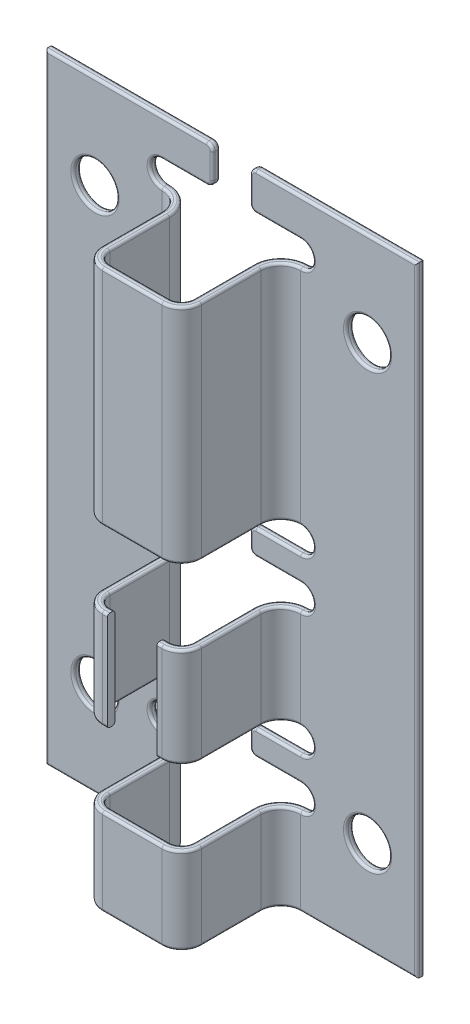
SolidWorks part; units mm, degrees
ref_plane "前视基准面" through (0, 0, 0) normal (0, 0, 1) x (1, 0, 0)
ref_plane "上视基准面" through (0, 0, 0) normal (0, 1, 0) x (1, 0, 0)
ref_plane "右视基准面" through (0, 0, 0) normal (1, 0, 0) x (0, 0, -1)
sketch "草图1" plane through (0, 0, 0) normal (0, 0, 1) x (1, 0, 0)
  line L0 (0, 0) -> (0, 23.061) construction
  line L1 (-15, 25) -> (15, 25)
  line L2 (-15, 25) -> (-15, -25)
  line L3 (-15, -25) -> (15, -25)
  line L4 (15, 25) -> (15, -25)
  line L5 (0, 0) -> (13.1803, 0) construction
  circle A0 centre (11, 17.5) radius 1.75
  circle A1 centre (-11, 17.5) radius 1.75
  circle A2 centre (11, -17.5) radius 1.75
  circle A3 centre (-11, -17.5) radius 1.75
  dimension "D3" = 3.5
  dimension "D4" = 22
  dimension "D5" = 35
  dimension "D1" = 30
  dimension "D2" = 50
extrude "凸台-拉伸1" add sketch "草图1" along normal blind 0.6
sketch "草图3" plane through (0, 25, 0) normal (0, 1, 0) x (1, 0, 0)
  line L0 (-4, -0.6) -> (-4, -8.6)
  line L1 (15, -0.6) -> (-15, -0.6) construction
  line L2 (-4, -8.6) -> (4, -8.6)
  line L3 (4, -8.6) -> (4, -0.6)
  line L4 (0, 0) -> (0, -3.0112) construction
  line L5 (-3.4, -0.6) -> (-3.4, -8)
  line L6 (-3.4, -8) -> (3.4, -8)
  line L7 (3.4, -8) -> (3.4, -0.6)
  line L8 (-4, -0.6) -> (-3.4, -0.6)
  line L9 (4, -0.6) -> (3.4, -0.6)
  dimension "D1" = 8
  dimension "D2" = 8
  dimension "D3" = 0.6
extrude "凸台-拉伸2" add sketch "草图3" against normal up to surface (50 mm away) up to face at (0, -25, 0.3)
sketch "草图4" plane through (0, 0, 8.6) normal (0, 0, 1) x (1, 0, 0)
  line L0 (4, -25) -> (4, 25) construction
  line L1 (-4, 25) -> (4, 25)
  line L2 (-4, 25) -> (-4, 20)
  line L3 (-4, 20) -> (4, 20)
  line L4 (4, 25) -> (4, 20)
  line L5 (-4, -25) -> (-4, 25) construction
  line L6 (-4, 2) -> (4, 2)
  line L7 (-4, 2) -> (-4, -4)
  line L8 (-4, -4) -> (4, -4)
  line L9 (4, 2) -> (4, -4)
  line L10 (4, -25) -> (4, 25) construction
  line L11 (-4, -25) -> (-4, 25) construction
  line L12 (-4, -12) -> (4, -12)
  line L13 (-4, -12) -> (-4, -18)
  line L14 (-4, -18) -> (4, -18)
  line L15 (4, -12) -> (4, -18)
  dimension "D1" = 5
  dimension "D2" = 18
  dimension "D3" = 6
  dimension "D4" = 8
  dimension "D5" = 6
extrude "切除-拉伸1" cut sketch "草图4" against normal up to surface (8 mm away) up to face at (9.5, 0, 0.6)
fillet "圆角1" radius 1 6 edges at (3.4, -21.5, 8) (-3.4, -21.5, 8) (-3.4, -8, 8) (3.4, -8, 8) (3.4, 11, 8) (-3.4, 11, 8)
fillet "圆角2" radius 1.6 6 edges at (-4, -21.5, 8.6) (4, -21.5, 8.6) (-4, -8, 8.6) (4, -8, 8.6) (4, 11, 8.6) (-4, 11, 8.6)
fillet "圆角3" radius 1.6 6 edges at (4, 11, 0.6) (4, -8, 0.6) (4, -21.5, 0.6) (-4, -21.5, 0.6) (-4, -8, 0.6) (-4, 11, 0.6)
sketch "草图5" plane through (0, 0, 0.6) normal (0, 0, 1) x (1, 0, 0)
  line L1 (-5.6, 20) -> (5.6, 20)
  line L3 (-5.6, 22) -> (5.6, 22)
  arc A0 (-5.6, 22) -> (-5.6, 20) centre (-5.6, 21) ccw
  arc A1 (5.6, 20) -> (5.6, 22) centre (5.6, 21) ccw
  dimension "D1" = 2
  dimension "D2" = 2
extrude "切除-拉伸2" cut sketch "草图5" against normal up to surface (0.6 mm away) up to face at (12.75, -17.5, 0)
pattern_linear "阵列(线性)1" count 2 spacing 20 along (0, -1, 0) of "切除-拉伸2"
pattern_linear "阵列(线性)2" count 2 spacing 24 along (0, -1, 0) of "切除-拉伸2"
pattern_linear "阵列(线性)3" count 2 spacing 34 along (0, -1, 0) of "切除-拉伸2"
pattern_linear "阵列(线性)4" count 2 spacing 38 along (0, -1, 0) of "切除-拉伸2"
sketch "草图7" plane through (0, 0, 0.6) normal (0, 0, 1) x (1, 0, 0)
  line L4 (3.4, -18) -> (-3.4, -18)
  line L5 (-3.4, -18) -> (-3.4, -25)
  line L6 (-3.4, -25) -> (3.4, -25)
  line L7 (3.4, -25) -> (3.4, -18)
  line L8 (3.4, -18) -> (-3.4, -18)
  line L9 (-3.4, -18) -> (-3.4, -25)
  line L10 (-3.4, -25) -> (3.4, -25)
  line L11 (3.4, -25) -> (3.4, -18)
  line L12 (-3.4, -12) -> (3.4, -12)
  line L13 (3.4, -12) -> (3.4, -4)
  line L14 (3.4, -4) -> (-3.4, -4)
  line L15 (-3.4, -4) -> (-3.4, -12)
  line L16 (-3.4, -12) -> (3.4, -12)
  line L17 (3.4, -12) -> (3.4, -4)
  line L18 (3.4, -4) -> (-3.4, -4)
  line L19 (-3.4, -4) -> (-3.4, -12)
  line L20 (-3.4, 2) -> (3.4, 2)
  line L21 (3.4, 2) -> (3.4, 20)
  line L22 (3.4, 20) -> (-3.4, 20)
  line L23 (-3.4, 20) -> (-3.4, 2)
  line L24 (-3.4, 2) -> (3.4, 2)
  line L25 (3.4, 2) -> (3.4, 20)
  line L26 (3.4, 20) -> (-3.4, 20)
  line L27 (-3.4, 20) -> (-3.4, 2)
  dimension "D1" = 0
  dimension "D2" = 0
  dimension "D3" = 0
extrude "切除-拉伸4" cut sketch "草图7" against normal up to surface (0.6 mm away) up to face at (0, -17, 0)
sketch "草图8" plane through (0, 0, 0) normal (0, 0, -1) x (-1, 0, 0)
  line L0 (-15, 25) -> (15, 25) construction
  line L1 (-1.5, 25) -> (1.5, 25)
  line L2 (-1.5, 25) -> (-1.5, -25)
  line L3 (-1.5, -25) -> (1.5, -25)
  line L4 (1.5, 25) -> (1.5, -25)
  line L5 (2.4, -25) -> (-2.4, -25) construction
  point P8 (0, 25)
  dimension "D1" = 3
extrude "切除-拉伸5" cut sketch "草图8" against normal up to surface (0.6 mm away) up to face at (0, -11.8, 0.6)
fillet "圆角4" radius 2.2 6 edges at (-3.4, -21.5, 0) (3.4, -21.5, 0) (-3.4, -8, 0) (3.4, -8, 0) (-3.4, 11, 0) (3.4, 11, 0)
fillet "圆角5" radius 0.2 156 edges at (-4.4686, -12, 1.0686) (-4, -12, 4.6) (-3.5314, -12, 8.1314) (0, -12, 8.6) (3.5314, -12, 8.1314) (4, -12, 4.6) (4.4686, -12, 1.0686) (-4.4686, -4, 1.0686) (-4, -4, 4.6) (-3.5314, -4, 8.1314) (0, -4, 8.6) (3.5314, -4, 8.1314) (4, -4, 4.6) (4.4686, -4, 1.0686) (-4.4686, 2, 1.0686) (-4, 2, 4.6) (-3.5314, 2, 8.1314) (0, 2, 8.6) (3.5314, 2, 8.1314) (4, 2, 4.6) (4.4686, 2, 1.0686) (-4.4686, 20, 1.0686) (-4, 20, 4.6) (-3.5314, 20, 8.1314) (0, 20, 8.6) (3.5314, 20, 8.1314) (4, 20, 4.6) (4.4686, 20, 1.0686) (-4.4686, -25, 1.0686) (-4, -25, 4.6) (-3.5314, -25, 8.1314) (0, -25, 8.6) (3.5314, -25, 8.1314) (4, -25, 4.6) (4.4686, -25, 1.0686) (-4.4686, -18, 1.0686) (-4, -18, 4.6) (-3.5314, -18, 8.1314) (0, -18, 8.6) (3.5314, -18, 8.1314) (4, -18, 4.6) (4.4686, -18, 1.0686) (-9.25, -17.5, 0.6) (-9.25, 17.5, 0.6) (-3.55, 22, 0.6) (-6.6, 21, 0.6) (-6.6, 1, 0.6) (-3.55, 0, 0.6) (-1.5, -1, 0.6) (-3.55, -2, 0.6) (-6.6, -3, 0.6) (-6.6, -13, 0.6) (-3.55, -14, 0.6) (-1.5, -15, 0.6) (-3.55, -16, 0.6) (-6.6, -17, 0.6) (-10.3, -25, 0.6) (-15, 0, 0.6) (-8.25, 25, 0.6) (-1.5, 23.5, 0.6) (12.75, 17.5, 0.6) (12.75, -17.5, 0.6) (3.55, -14, 0.6) (6.6, -13, 0.6) (6.6, -3, 0.6) (3.55, -2, 0.6) (1.5, -1, 0.6) (3.55, 0, 0.6) (6.6, 1, 0.6) (6.6, 21, 0.6) (3.55, 22, 0.6) (1.5, 23.5, 0.6) (8.25, 25, 0.6) (15, 0, 0.6) (10.3, -25, 0.6) (6.6, -17, 0.6) (3.55, -16, 0.6) (1.5, -15, 0.6) (4.0444, -12, 0.6444) (3.4, -12, 4.6) (3.1071, -12, 7.7071) (0, -12, 8) (-3.1071, -12, 7.7071) (-3.4, -12, 4.6) (-4.0444, -12, 0.6444) (4.0444, -4, 0.6444) (3.4, -4, 4.6) (3.1071, -4, 7.7071) (0, -4, 8) (-3.1071, -4, 7.7071) (-3.4, -4, 4.6) (-4.0444, -4, 0.6444) (4.0444, 2, 0.6444) (3.4, 2, 4.6) (3.1071, 2, 7.7071) (0, 2, 8) (-3.1071, 2, 7.7071) (-3.4, 2, 4.6) (-4.0444, 2, 0.6444) (4.0444, 20, 0.6444) (3.4, 20, 4.6) (3.1071, 20, 7.7071) (0, 20, 8) (-3.1071, 20, 7.7071) (-3.4, 20, 4.6) (-4.0444, 20, 0.6444) (4.0444, -25, 0.6444) (3.4, -25, 4.6) (3.1071, -25, 7.7071) (0, -25, 8) (-3.1071, -25, 7.7071) (-3.4, -25, 4.6) (-4.0444, -25, 0.6444) (4.0444, -18, 0.6444) (3.4, -18, 4.6) (3.1071, -18, 7.7071) (0, -18, 8) (-3.1071, -18, 7.7071) (-3.4, -18, 4.6) (-4.0444, -18, 0.6444) (12.75, 17.5, 0) (12.75, -17.5, 0) (15, 0, 0) (8.25, 25, 0) (1.5, 23.5, 0) (3.55, 22, 0) (6.6, 21, 0) (6.6, 1, 0) (3.55, 0, 0) (1.5, -1, 0) (3.55, -2, 0) (6.6, -3, 0) (6.6, -13, 0) (3.55, -14, 0) (1.5, -15, 0) (3.55, -16, 0) (6.6, -17, 0) (10.3, -25, 0) (-3.55, -16, 0) (-1.5, -15, 0) (-3.55, -14, 0) (-6.6, -13, 0) (-6.6, -3, 0) (-3.55, -2, 0) (-1.5, -1, 0) (-3.55, 0, 0) (-6.6, 1, 0) (-6.6, 21, 0) (-3.55, 22, 0) (-1.5, 23.5, 0) (-8.25, 25, 0) (-15, 0, 0) (-10.3, -25, 0) (-6.6, -17, 0) (-9.25, 17.5, 0) (-9.25, -17.5, 0)
fillet "圆角6" radius 0.5 36 edges at (-1.5586, 24.9414, 0.5414) (1.5586, 24.9414, 0.5414) (1.5586, 22.0586, 0.5414) (-1.5586, 22.0586, 0.5414) (-1.5586, -1.9414, 0.0586) (-1.5586, -0.0586, 0.0586) (1.5586, -15.9414, 0.0586) (1.5586, -14.0586, 0.0586) (-1.5586, -14.0586, 0.0586) (-1.5586, -15.9414, 0.0586) (-1.5586, 24.9414, 0.0586) (1.5586, 24.9414, 0.0586) (1.5586, 22.0586, 0.0586) (-1.5586, 22.0586, 0.0586) (1.5586, -1.9414, 0.0586) (1.5586, -1.9414, 0.5414) (1.5586, -0.0586, 0.5414) (1.5586, -0.0586, 0.0586) (-1.5586, -1.9414, 0.5414) (-1.5586, -0.0586, 0.5414) (1.5586, -15.9414, 0.5414) (1.5586, -14.0586, 0.5414) (-1.5586, -14.0586, 0.5414) (-1.5586, -15.9414, 0.5414) (-1.5, -16, 0.3) (-1.5, -14, 0.3) (1.5, -14, 0.3) (1.5, -16, 0.3) (-1.5, 0, 0.3) (-1.5, -2, 0.3) (-1.5, 22, 0.3) (1.5, 22, 0.3) (1.5, 25, 0.3) (-1.5, 25, 0.3) (1.5, 0, 0.3) (1.5, -2, 0.3)
sketch "草图9" plane through (0, 0, 8.6) normal (0, 0, 1) x (1, 0, 0)
  line L0 (0, 0) -> (0, -8.8218) construction
  line L1 (-2, -2.9785) -> (2, -2.9785)
  line L2 (-2, -2.9785) -> (-2, -13.0692)
  line L3 (-2, -13.0692) -> (2, -13.0692)
  line L4 (2, -2.9785) -> (2, -13.0692)
  dimension "D1" = 4
extrude "切除-拉伸6" cut sketch "草图9" against normal up to surface (8.6 mm away) up to face at (12.95, 17.5, 0)
